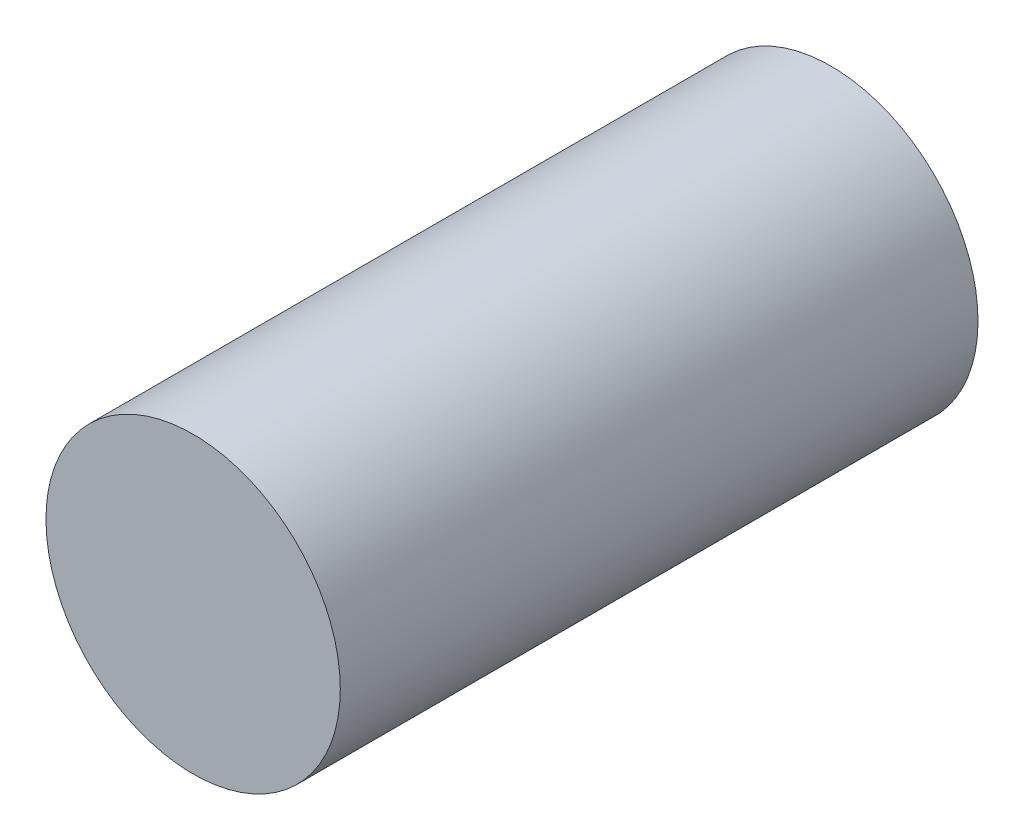
SolidWorks part; units mm, degrees
ref_plane "Płaszczyzna przednia" through (0, 0, 0) normal (0, 0, 1) x (1, 0, 0)
ref_plane "Płaszczyzna górna" through (0, 0, 0) normal (0, 1, 0) x (1, 0, 0)
ref_plane "Płaszczyzna prawa" through (0, 0, 0) normal (1, 0, 0) x (0, 0, -1)
sketch "Szkic1" plane through (0, 0, 0) normal (0, 0, 1) x (1, 0, 0)
  circle A0 centre (0, 0) radius 3
  dimension "D1" = 6
extrude "Dodanie-wyciągnięcie1" add sketch "Szkic1" along normal blind 13
sketch "Szkic2" plane through (0, 0, 13) normal (0, 0, 1) x (1, 0, 0)
  circle A0 centre (0, 0) radius 3.83
  dimension "D1" = 7.66
extrude "Dodanie-wyciągnięcie2" add sketch "Szkic2" along normal blind 9
thread "Gwint1" pitch 1.25 method extrude profile "Profil gwintu1" start angle 0, offset 0, length 10, pitch 1.25, diameter 7.66
ref_plane "Płaszczyzna4" through (3.83, 0, 13) normal (0, -1, 0) x (1, 0, 0)
sketch "Profil gwintu1" plane through (3.83, 0, 13) normal (0, -1, 0) x (1, 0, 0)
  line L0 (0, 0) -> (0, 1.25) construction
  line L1 (0, 0) -> (0.6766, 0.3906)
  line L2 (0.6766, 0.3906) -> (0.6766, 0.5469)
  line L3 (0.6766, 0.5469) -> (0, 0.9375)
  line L4 (0.6766, 0.4687) -> (0, 0.4687) construction
  line L11 (0, 0) -> (0, 0.9375)
  point P2 (0, 0)
  dimension "Pitch" = 1.25
  dimension "Profile_Angle" = 60
  dimension "Profile_Land" = 0.1562
  dimension "Profile_Height" = 0.6766
sketch "Szkic6" plane through (0, 0, 22) normal (0, 0, 1) x (1, 0, 0)
  circle A0 centre (0, 0) radius 6
  dimension "D1" = 12
extrude "Dodanie-wyciągnięcie3" add sketch "Szkic6" along normal blind 2
sketch "Szkic8" plane through (0, 0, 24) normal (0, 0, 1) x (1, 0, 0)
  line L0 (0, 9) -> (-7.94, 9) construction
  line L1 (-7.94, 9) -> (7.94, 9)
  line L2 (-7.94, 9) -> (-7.94, -12.21)
  line L3 (-7.94, -12.21) -> (7.94, -12.21)
  line L4 (7.94, 9) -> (7.94, -12.21)
  line L5 (0, -12.21) -> (0, 9) construction
  dimension "D1" = 15.88
  dimension "D2" = 21.21
  dimension "D3" = 9
extrude "Dodanie-wyciągnięcie4" add sketch "Szkic8" along normal blind 14
fillet "Zaokrąglenie1" radius 2 8 edges at (7.94, -1.605, 24) (0, -12.21, 24) (-7.94, -1.605, 24) (0, 9, 24) (-7.94, -12.21, 31) (7.94, -12.21, 31) (-7.94, 9, 31) (7.94, 9, 31)
sketch "Szkic9" plane through (0, 0, 0) normal (0, 0, -1) x (-1, 0, 0)
  line L0 (-1.5964, -2.54) -> (1.5964, -2.54)
  line L1 (-1.5964, -2.54) -> (-7.8481, -6.1903)
  line L2 (-7.8481, -6.1903) -> (8.0345, -6.6875)
  line L3 (8.0345, -6.6875) -> (1.5964, -2.54)
  circle A0 centre (0, 0) radius 3 construction
  circle A1 centre (0, 0) radius 3 construction
  point P4 (0, 3)
  dimension "D1" = 5.54
extrude "Wytnij-wyciągnięcie1" cut sketch "Szkic9" against normal blind 9
sketch "Szkic10" plane through (0, 0, 0) normal (0, 0, 1) x (1, 0, 0)
  line L0 (0, 0) -> (7.94, 0) construction
  line L1 (7.94, -0.8464) -> (7.94, 0.8464) construction
  line L2 (7.94, 0) -> (7.94, 1)
  line L3 (7.94, 0) -> (7.94, -1)
  arc A0 (7.94, 1) -> (7.94, -1) centre (7.94, 0) ccw
  dimension "D1" = 1
  dimension "D2" = 1
  dimension "D3" = 7.94
extrude "Dodanie-wyciągnięcie6" add sketch "Szkic10" along normal up to next from surface starting at face at (0, 5.2116, 24)
extrude "Dodanie-wyciągnięcie7" add sketch "Szkic10<2>" against normal blind 1 from surface starting at face at (0, -6.8166, 24)
sketch "Szkic10<2>" plane through (0, 0, 0) normal (0, 0, 1) x (1, 0, 0) same geometry as "Szkic10"
sketch "Szkic11" plane through (0, 0, 0) normal (0, 0, -1) x (-1, 0, 0)
  circle A0 centre (0, 0) radius 50
  dimension "D1" = 100
extrude "Wytnij-wyciągnięcie2" cut sketch "Szkic11" against normal through all from surface body kept at (3, 0, 0) starting at face at (3, 0, 13)
